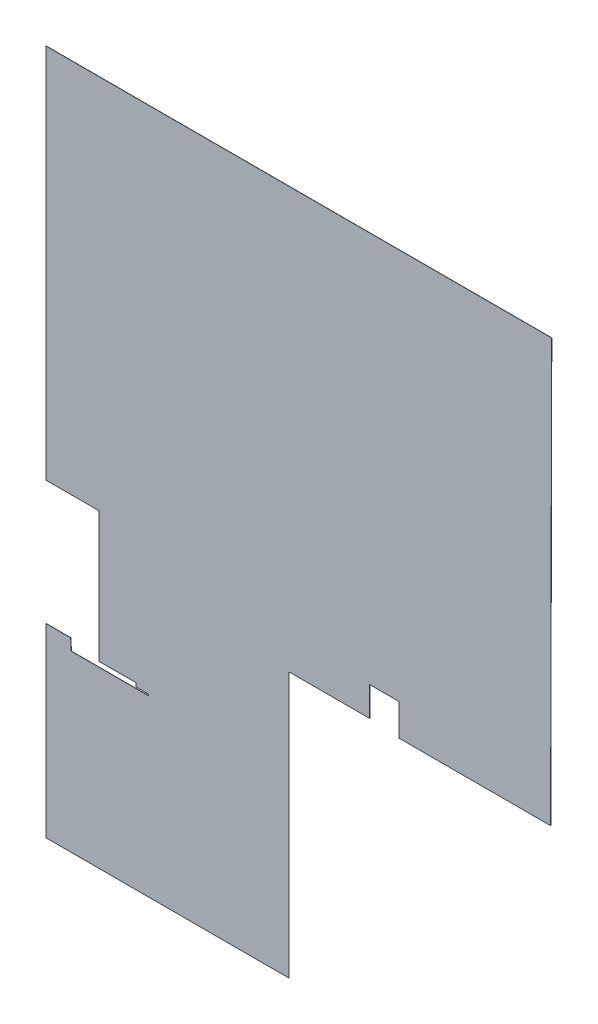
SolidWorks part; units mm, degrees
ref_plane "Alzado" through (0, 0, 0) normal (0, 0, 1) x (1, 0, 0)
ref_plane "Planta" through (0, 0, 0) normal (0, 1, 0) x (1, 0, 0)
ref_plane "Vista lateral" through (0, 0, 0) normal (1, 0, 0) x (0, 0, -1)
sketch "Croquis1" plane through (0, 0, 0) normal (0, 0, 1) x (1, 0, 0)
  line L0 (0, 0) -> (25000, 0)
  line L1 (25000, 0) -> (24950, -20920.8041)
  line L7 (12000, -20800.8041) -> (12000, -33920.8041)
  line L8 (12000, -33920.8041) -> (0, -33920.8041)
  line L9 (0, -33920.8041) -> (0, -24740.8041)
  line L10 (0, -24740.8041) -> (1210, -24740.8041)
  line L11 (1210, -24740.8041) -> (1240, -25300)
  line L12 (1240, -25300) -> (5070, -25300)
  line L13 (5070, -25300) -> (5070, -25230)
  line L15 (16000, -20800.8041) -> (16000, -19350.8041)
  line L16 (5070, -25230) -> (4440, -25230)
  line L17 (4440, -25230) -> (4440, -25050)
  line L18 (4440, -25050) -> (2600, -25050)
  line L19 (2600, -25050) -> (2600, -18600)
  line L20 (2600, -18600) -> (0, -18600)
  line L21 (0, -18600) -> (0, 0)
  line L22 (16000, -19350.8041) -> (17450, -19350.8041)
  line L23 (17450, -19350.8041) -> (17450, -20920.8041)
  line L24 (17450, -20920.8041) -> (24950, -20920.8041)
  line L26 (12000, -20800.8041) -> (16000, -20800.8041)
  point P5 (15455.5504, -20001.982)
  point P17 (15506.2902, -20534.8102)
  dimension "D1" = 25000
  dimension "D3" = 13120
  dimension "D4" = 7500
  dimension "D5" = 1450
  dimension "D6" = 1570
  dimension "D7" = 1450
  dimension "D8" = 4000
  dimension "D9" = 12000
  dimension "D10" = 9180
  dimension "D11" = 1210
  dimension "D12" = 560
  dimension "D13" = 3830
  dimension "D14" = 18600
  dimension "D15" = 2600
  dimension "D16" = 6450
  dimension "D17" = 180
  dimension "D18" = 630
  dimension "D19" = 1840
  dimension "D20" = 70
extrude "Saliente-Extruir1" add sketch "Croquis1" along normal blind 10
